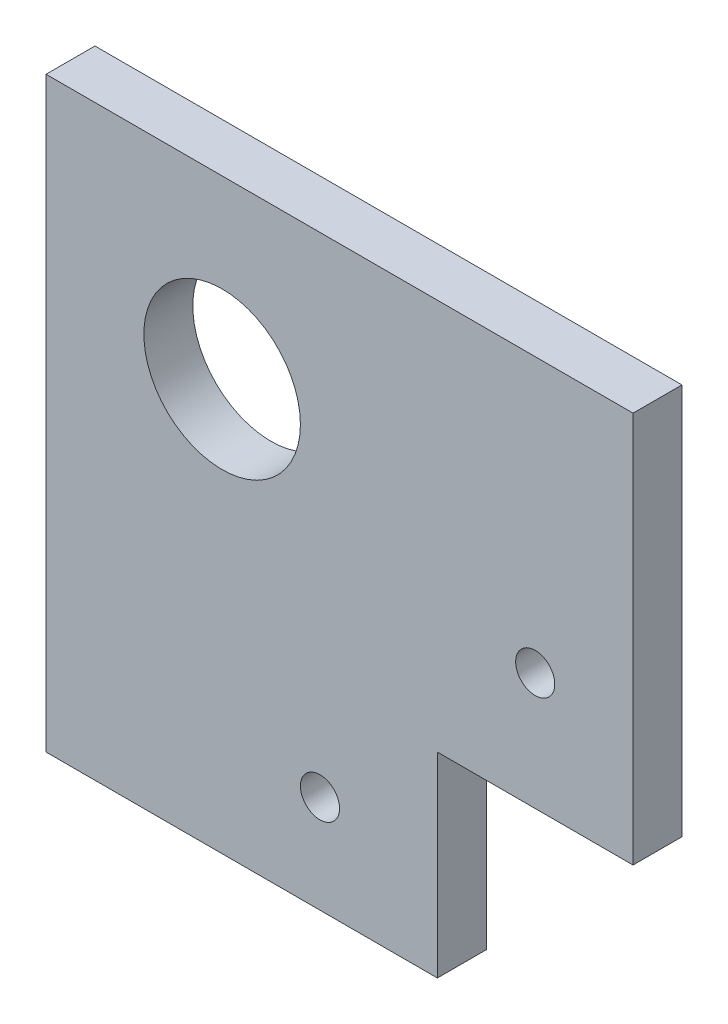
SolidWorks part; units mm, degrees
ref_plane "Płaszczyzna przednia" through (0, 0, 0) normal (0, 0, 1) x (1, 0, 0)
ref_plane "Płaszczyzna górna" through (0, 0, 0) normal (0, 1, 0) x (1, 0, 0)
ref_plane "Płaszczyzna prawa" through (0, 0, 0) normal (1, 0, 0) x (0, 0, -1)
sketch "Sketch1" plane through (0, 0, 0) normal (0, 0, 1) x (1, 0, 0)
  line L1 (0, 0) -> (40, 0)
  line L2 (0, 0) -> (0, 60)
  line L3 (0, 60) -> (60, 60)
  line L4 (60, 20) -> (60, 60)
  line L5 (0, 0) -> (60, 60) construction
  line L6 (0, 60) -> (60, 0) construction
  line L9 (60, 20) -> (40, 20)
  line L10 (40, 0) -> (40, 20)
  line L11 (60, 0) -> (40, 20) construction
  line L12 (60, 20) -> (40, 0) construction
  circle A0 centre (18, 42) radius 8
  point P4 (30, 30)
  point P9 (50, 10)
  dimension "D5" = 16
  dimension "D6" = 42
  dimension "D7" = 42
  dimension "D1" = 60
  dimension "D2" = 60
  dimension "D3" = 20
  dimension "D4" = 20
extrude "Boss-Extrude1" add sketch "Sketch1" along normal blind 5
sketch "Sketch2" plane through (0, 0, 0) normal (0, 0, -1) x (-1, 0, 0)
  line L0 (-40, 20) -> (-60, 20) construction
  line L1 (-60, 20) -> (-60, 60) construction
  line L2 (0, 0) -> (-40, 0) construction
  line L3 (-40, 0) -> (-40, 20) construction
  circle A0 centre (-50, 32) radius 2
  circle A1 centre (-28, 10) radius 2
  dimension "D1" = 4
  dimension "D2" = 12
  dimension "D3" = 10
  dimension "D4" = 4
  dimension "D5" = 10
  dimension "D6" = 12
extrude "Cut-Extrude1" cut sketch "Sketch2" against normal through all
